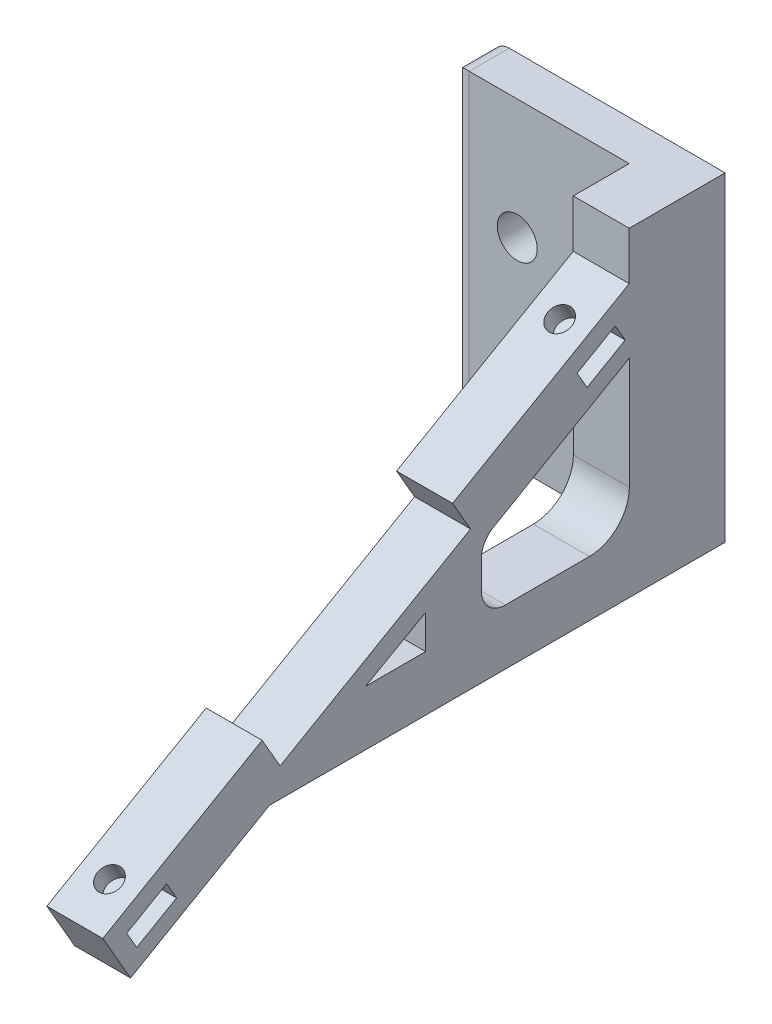
SolidWorks part; units mm, degrees
ref_plane "Front Plane" through (0, 0, 0) normal (0, 0, 1) x (1, 0, 0)
ref_plane "Top Plane" through (0, 0, 0) normal (0, 1, 0) x (1, 0, 0)
ref_plane "Right Plane" through (0, 0, 0) normal (1, 0, 0) x (0, 0, -1)
sketch "Sketch1" plane through (0, 0, 0) normal (1, 0, 0) x (0, 0, -1)
  line L0 (0, 0) -> (0, 40)
  line L1 (0, 40) -> (-7, 40)
  line L2 (-7, 40) -> (-7, 34)
  line L3 (-7, 34) -> (-29.0836, 21.25)
  line L4 (-29.0836, 21.25) -> (-26.8336, 17.3529)
  line L5 (-26.8336, 17.3529) -> (-50.6493, 3.6029)
  line L6 (-50.6493, 3.6029) -> (-52.8993, 7.5)
  line L7 (-52.8993, 7.5) -> (-72.8179, -4)
  line L8 (-72.8179, -4) -> (-69.3455, -10.0144)
  line L9 (-69.3455, -10.0144) -> (-52, 0)
  line L10 (-52, 0) -> (0, 0)
  line L11 (-69.8283, -4.9261) -> (-64.8487, -2.0511)
  line L12 (-64.8487, -2.0511) -> (-63.5987, -4.2162)
  line L13 (-63.5987, -4.2162) -> (-68.5783, -7.0912)
  line L14 (-68.5783, -7.0912) -> (-69.8283, -4.9261)
  line L15 (-39.9499, 6.884) -> (-32.4499, 11.134)
  line L16 (-32.4499, 11.134) -> (-32.4499, 6.884)
  line L17 (-32.4499, 6.884) -> (-39.9499, 6.884)
  line L18 (-6.98, 25.947) -> (-6.98, 11.947)
  line L19 (-11.98, 6.947) -> (-22.48, 6.947)
  line L20 (-25.48, 9.947) -> (-25.48, 13.5056)
  line L21 (-6.98, 25.947) -> (-23.98, 16.107)
  line L22 (-13.5125, 27.5567) -> (-8.7524, 30.3119)
  line L23 (-8.7524, 30.3119) -> (-7.5, 28.1483)
  line L24 (-7.5, 28.1483) -> (-12.2601, 25.393)
  line L25 (-12.2601, 25.393) -> (-13.5125, 27.5567)
  arc A0 (-6.98, 11.947) -> (-11.98, 6.947) centre (-11.98, 11.947) cw
  arc A1 (-22.48, 6.947) -> (-25.48, 9.947) centre (-22.48, 9.947) cw
  arc A2 (-25.48, 13.5056) -> (-23.98, 16.107) centre (-22.4743, 13.5056) cw
  dimension "D19" = 5
  dimension "D20" = 3
  dimension "D22" = 9.84
  dimension "D1" = 40
  dimension "D2" = 7
  dimension "D3" = 6
  dimension "D4" = 25.5
  dimension "D5" = 4.5
  dimension "D6" = 27.5
  dimension "D7" = 4.5
  dimension "D8" = 23
  dimension "D9" = 52
  dimension "D10" = 150
  dimension "D11" = 2.148
  dimension "D12" = 2.126
  dimension "D13" = 2.5
  dimension "D14" = 5.75
  dimension "D15" = 7.5
  dimension "D16" = 4.25
  dimension "D17" = 32.868
  dimension "D18" = 6.884
  dimension "D21" = 10.5
  dimension "D23" = 17
  dimension "D24" = 11.98
  dimension "D25" = 25.947
  dimension "D26" = 19
  dimension "D27" = 5.5
  dimension "D28" = 2.5
  dimension "D29" = 7.5
  dimension "D30" = 25.393
extrude "Boss-Extrude1" add sketch "Sketch1" against normal blind 7
sketch "Sketch2" plane through (0, 0, 0) normal (0, 0, -1) x (-1, 0, 0)
  line L0 (0, 40) -> (29, 40)
  line L1 (29, 40) -> (29, 0)
  line L2 (29, 0) -> (0, 0)
  line L3 (0, 0) -> (0, 40)
  line L4 (21, 5) -> (21, 25) construction
  circle A0 centre (21, 25) radius 2.5
  circle A1 centre (21, 5) radius 2.5
  dimension "D2" = 5
  dimension "D3" = 5
  dimension "D1" = 29
  dimension "D4" = 35
  dimension "D5" = 20
  dimension "D6" = 8
extrude "Boss-Extrude2" add sketch "Sketch2" along normal blind 5
fillet "Fillet1" radius 2 3 edges at (-29, 0, -2.5) (-29, 20, 0) (-29, 40, -2.5)
sketch "Sketch3" plane through (0, 28.5311, 16.4724) normal (0, 0.866, 0.5) x (1, 0, 0)
  line L0 (-3.5, 4.9378) -> (-3.5, -60.0622) construction
  line L1 (-7, 10.9378) -> (0, 10.9378) construction
  line L2 (0, 10.9378) -> (0, -14.5622) construction
  circle A0 centre (-3.5, 4.9378) radius 1.5
  circle A1 centre (-3.5, -60.0622) radius 1.5
  dimension "D1" = 3
  dimension "D2" = 3
  dimension "D3" = 65
  dimension "D4" = 6
  dimension "D5" = 3.5
extrude "Cut-Extrude1" cut sketch "Sketch3" against normal blind 7.5
